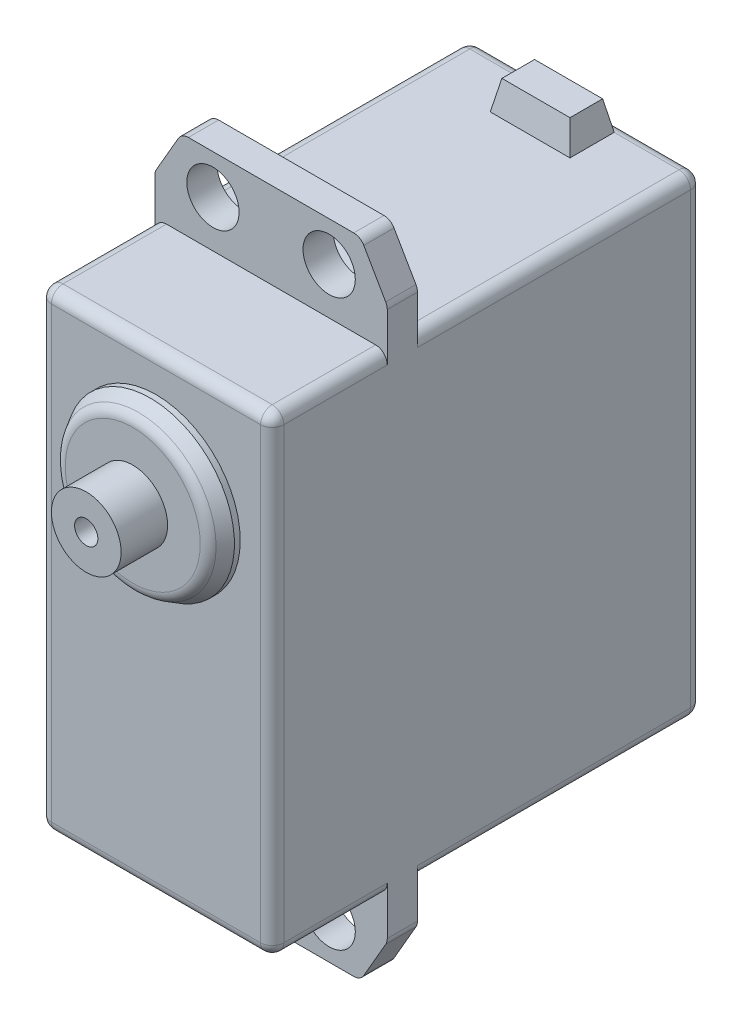
SolidWorks part; units mm, degrees
ref_plane "Front Plane" through (0, 0, 0) normal (0, 0, 1) x (1, 0, 0)
ref_plane "Top Plane" through (0, 0, 0) normal (0, 1, 0) x (1, 0, 0)
ref_plane "Right Plane" through (0, 0, 0) normal (1, 0, 0) x (0, 0, -1)
sketch "Sketch3" plane through (0, 0, 0) normal (0, 0, 1) x (1, 0, 0)
  line L0 (-5, 24.3) -> (-5, -24.3) construction
  line L1 (-10, 27.7) -> (10, 27.7)
  line L2 (-10, 27.7) -> (-10, -27.7)
  line L3 (-10, -27.7) -> (0, -27.7)
  line L4 (0, 27.7) -> (0, -27.7) construction
  line L5 (5, 24.3) -> (5, -24.3) construction
  line L6 (-10, 20.3) -> (10, 20.3)
  line L7 (-10, 20.3) -> (-10, -20.3)
  line L8 (-10, -20.3) -> (10, -20.3)
  line L10 (10, 20.3) -> (10, -20.3)
  line L11 (10, -27.7) -> (0, -27.7)
  line L12 (10, 27.7) -> (10, -27.7)
  circle A0 centre (-5, 24.3) radius 2.25
  circle A1 centre (-5, -24.3) radius 2.25
  circle A2 centre (5, -24.3) radius 2.25
  circle A3 centre (5, 24.3) radius 2.25
  circle A4 centre (0, 9.8) radius 3
  circle A7 centre (0, 9.8) radius 7.25
  circle A8 centre (0, 9.8) radius 1
  point P6 (0, 0)
  point P10 (-5, 0)
  point P11 (-5, -27.7)
  point P16 (-10, 0)
  dimension "D3" = 4.5
  dimension "D4" = 4.5
  dimension "D5" = 48.6
  dimension "D7" = 14.5
  dimension "D8" = 6
  dimension "D9" = 14.5
  dimension "D10" = 2
  dimension "D1" = 55.4
  dimension "D2" = 10
  dimension "D6" = 40.6
extrude "Boss-Extrude1" add sketch "Sketch3" against normal blind 37 contours L10 L6 L2 L8 A4 | A4 | A4 | A8 region at (0, -2.5017, 0) region at (-2.9151, 9.8, 0) region at (-7.0449, 9.8, 0)
extrude "Boss-Extrude2" add sketch "Sketch3<3>" against normal blind 12.5 contours L12 L1 L2 L6 A0 A3 | L12 L8 L2 L3 L11 A1 A2 region at (0, 23.9179, 0) region at (0, -23.9179, 0)
sketch "Sketch3<3>" plane through (0, 0, 0) normal (0, 0, 1) x (1, 0, 0) same geometry as "Sketch3"
extrude "Cut-Extrude1" cut sketch "Sketch3<4>" against normal blind 9.9 contours L12 L1 L2 L6 A0 A3 | L12 L8 L2 L3 L11 A1 A2 region at (0, 23.9179, 0) region at (0, -23.9179, 0)
sketch "Sketch3<4>" plane through (0, 0, 0) normal (0, 0, 1) x (1, 0, 0) same geometry as "Sketch3"
extrude "Boss-Extrude3" add sketch "Sketch3<5>" along normal blind 6 contours A4 region at (-2.9151, 9.8, 0)
sketch "Sketch3<5>" plane through (0, 0, 0) normal (0, 0, 1) x (1, 0, 0) same geometry as "Sketch3"
extrude "Boss-Extrude4" add sketch "Sketch3<6>" along normal blind 2 contours A4 region at (-7.0449, 9.8, 0)
sketch "Sketch3<6>" plane through (0, 0, 0) normal (0, 0, 1) x (1, 0, 0) same geometry as "Sketch3"
chamfer "Chamfer1" distance 4 angle 30 4 edges at (10, -27.7, -11.2) (-10, -27.7, -11.2) (10, 27.7, -11.2) (-10, 27.7, -11.2) first distance on face at (10, 0, -13.6333) first distance on face at (-10, 0, -13.6333)
chamfer "Chamfer3" distance 1.5 angle 30 1 edges at (7.25, 9.8, 2) first distance on face at (7.25, 9.8, 2)
fillet "Fillet2" radius 1 25 edges at (10, 0, 0) (0, -20.3, 0) (-10, 0, 0) (0, 20.3, 0) (10, 23.7, -11.2) (7.6906, 27.7, -11.2) (-10, 23.7, -11.2) (-7.6906, 27.7, -11.2) (-7.6906, -27.7, -11.2) (-10, -23.7, -11.2) (10, -23.7, -11.2) (7.6906, -27.7, -11.2) (10, -20.3, -24.75) (0, -20.3, -37) (-10, 0, -37) (10, 0, -37) (0, 20.3, -37) (10, 20.3, -24.75) (-10, 20.3, -24.75) (10, -20.3, -4.95) (-10, -20.3, -24.75) (-10, -20.3, -4.95) (10, 20.3, -4.95) (-10, 20.3, -4.95) (6.384, 9.8, 2)
sketch "Sketch4" plane through (0, 20.3, 0) normal (0, 1, 0) x (1, 0, 0)
  line L0 (9, 36) -> (-9, 36) construction
  line L1 (-3.429, 36) -> (3.429, 36)
  line L2 (-3.429, 36) -> (-3.429, 32.19)
  line L3 (-3.429, 32.19) -> (3.429, 32.19)
  line L4 (3.429, 36) -> (3.429, 32.19)
  line L5 (-3.429, 36) -> (3.429, 32.19) construction
  line L6 (-3.429, 32.19) -> (3.429, 36) construction
  point P4 (0, 34.095)
  point P5 (0, 36)
  dimension "D1" = 6.858
  dimension "D2" = 3.81
extrude "Boss-Extrude6" add sketch "Sketch4" along normal blind 2.5
chamfer "Chamfer4" distance 2.5 distance2 0.5 4 edges at (0, 22.8, -32.19) (-3.429, 22.8, -34.095) (0, 22.8, -36) (3.429, 22.8, -34.095) first distance on face at (0, 21.55, -32.19) first distance on face at (-3.429, 21.55, -34.095) first distance on face at (0, 21.55, -36) first distance on face at (3.429, 21.55, -34.095)
